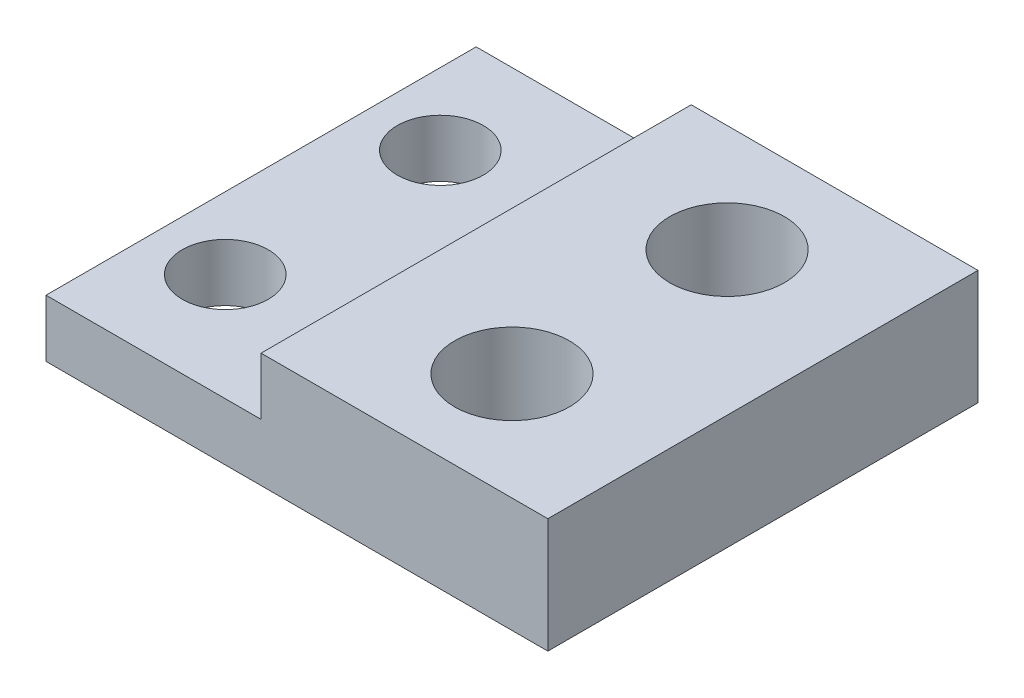
SolidWorks part; units mm, degrees
ref_plane "Alzado" through (0, 0, 0) normal (0, 0, 1) x (1, 0, 0)
ref_plane "Planta" through (0, 0, 0) normal (0, 1, 0) x (1, 0, 0)
ref_plane "Vista lateral" through (0, 0, 0) normal (1, 0, 0) x (0, 0, -1)
sketch "Croquis1" plane through (0, 0, 0) normal (0, 1, 0) x (1, 0, 0)
  line L1 (-10, 7.5) -> (10, 7.5)
  line L2 (-10, 7.5) -> (-10, -7.5)
  line L3 (-10, -7.5) -> (10, -7.5)
  line L4 (10, 7.5) -> (10, -7.5)
  line L5 (-10, 7.5) -> (10, -7.5) construction
  line L6 (-10, -7.5) -> (10, 7.5) construction
  circle A0 centre (-5, 3.75) radius 1.5
  circle A1 centre (-5, -3.75) radius 1.5
  circle A2 centre (5, 3.75) radius 2
  circle A3 centre (5, -3.75) radius 2
  point P0 (0, 0)
  point P14 (-26.9905, -11.8182)
  point P15 (-10.2605, -12.6685)
  point P16 (-11.6335, 13.6768)
  point P17 (22.6067, 3.7222)
  point P18 (26.3826, -9.3217)
  point P19 (-8.2641, -4.1321)
  point P20 (-8.2641, 4.1321)
  point P21 (0, 0)
  point P22 (7.4011, 3.7006)
  point P23 (7.4011, -3.7006)
  point P24 (0, 0)
  dimension "D1" = 3
  dimension "D2" = 3
  dimension "D3" = 4
  dimension "D4" = 4
  dimension "D5" = 20
  dimension "D6" = 15
  dimension "D7" = 5
  dimension "D8" = 5
extrude "Saliente-Extruir1" add sketch "Croquis1" along normal blind 4
sketch "Croquis3" plane through (0, 4, 0) normal (0, 1, 0) x (1, 0, 0)
  line L0 (-10, -7.5) -> (10, -7.5) construction
  line L1 (-10, 7.5) -> (0, 7.5)
  line L2 (-10, 7.5) -> (-10, -7.5)
  line L3 (-10, -7.5) -> (0, -7.5)
  line L4 (0, 7.5) -> (0, -7.5)
extrude "Cortar-Extruir1" cut sketch "Croquis3" against normal blind 2
sketch "Croquis4" plane through (0, 2, 0) normal (0, 1, 0) x (1, 0, 0)
  line L0 (-10, -7.5) -> (0, -7.5) construction
  line L1 (-10, 7.5) -> (-7.5, 7.5)
  line L2 (-10, 7.5) -> (-10, -7.5)
  line L3 (-10, -7.5) -> (-7.5, -7.5)
  line L4 (-7.5, 7.5) -> (-7.5, -7.5)
  dimension "D1" = 2.5
extrude "Cortar-Extruir2" cut sketch "Croquis4" against normal through all
